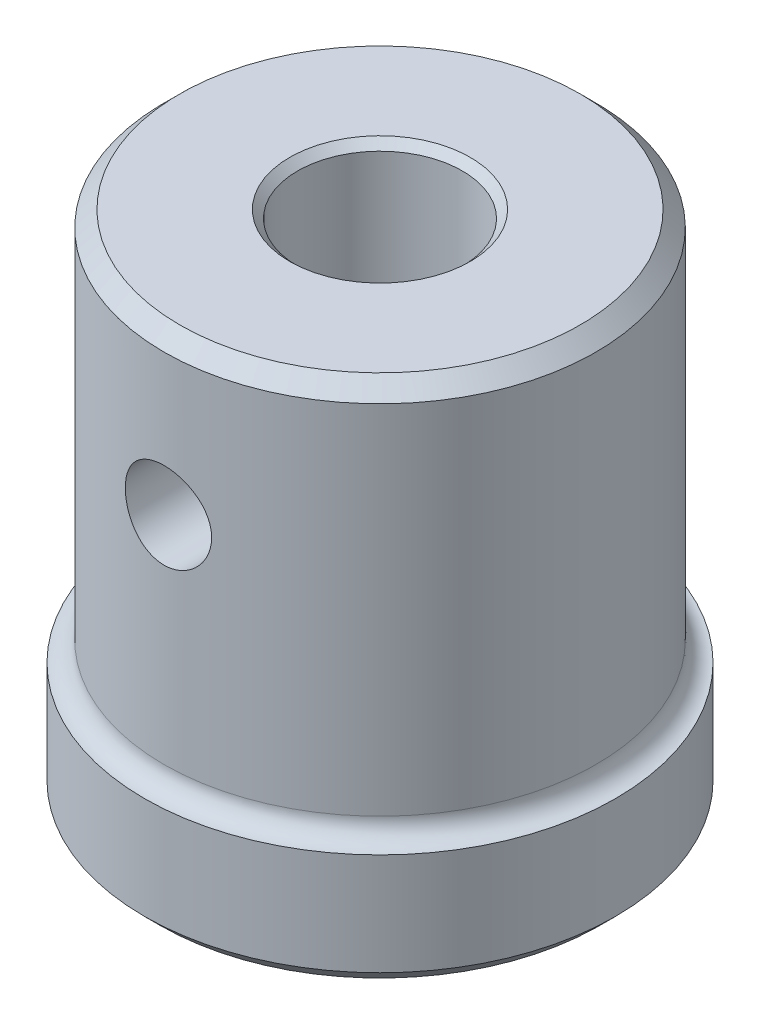
SolidWorks part; units mm, degrees
material "1.0060 (E335)"
ref_plane "Front Plane" through (0, 0, 0) normal (0, 0, 1) x (1, 0, 0)
ref_plane "Top Plane" through (0, 0, 0) normal (0, 1, 0) x (1, 0, 0)
ref_plane "Right Plane" through (0, 0, 0) normal (1, 0, 0) x (0, 0, -1)
sketch "Sketch1" plane through (0, 0, 0) normal (0, 1, 0) x (1, 0, 0)
  circle A0 centre (0, 0) radius 30
  dimension "D1" = 60
extrude "Boss-Extrude1" add sketch "Sketch1" along normal blind 15
sketch "Sketch2" plane through (0, 15, 0) normal (0, 1, 0) x (1, 0, 0)
  circle A0 centre (0, 0) radius 27.5
  dimension "D1" = 55
extrude "Boss-Extrude2" add sketch "Sketch2" along normal blind 50
sketch "Sketch3" plane through (0, 65, 0) normal (0, 1, 0) x (1, 0, 0)
  circle A0 centre (0, 0) radius 10.5
  dimension "D1" = 21
extrude "Cut-Extrude1" cut sketch "Sketch3" against normal blind 50
chamfer "Chamfer1" distance 2 angle 45 2 edges at (0, 65, 27.5) (0, 0, 30)
chamfer "Chamfer2" distance 1 angle 45 1 edges at (0, 65, 10.5)
fillet "Fillet1" radius 2.5 1 edges at (0, 15, 27.5)
sketch "Sketch4" plane through (0, 0, 0) normal (0, 0, 1) x (1, 0, 0)
  line L0 (0, -1000) -> (0, 49000) construction
  line L1 (0, 18) -> (-10.5, 18)
  line L2 (0, 15) -> (-10.5, 15)
  line L3 (0, 15) -> (0, 18)
  arc A0 (-10.5, 15) -> (-10.5, 18) centre (-10.5, 16.5) cw
  dimension "D1" = 3
  dimension "D2" = 21
  dimension "D3" = 15
revolve "Cut-Revolve1" cut sketch "Sketch4" angle 360 about L0
sketch "Sketch5" plane through (0, 0, 0) normal (0, 0, 1) x (1, 0, 0)
  line L0 (25.5, 65) -> (-25.5, 65) construction
  circle A0 centre (0, 45) radius 5.5
  dimension "D1" = 11
  dimension "D2" = 20
extrude "Cut-Extrude2" cut sketch "Sketch5" against normal through all both and the other way through all
